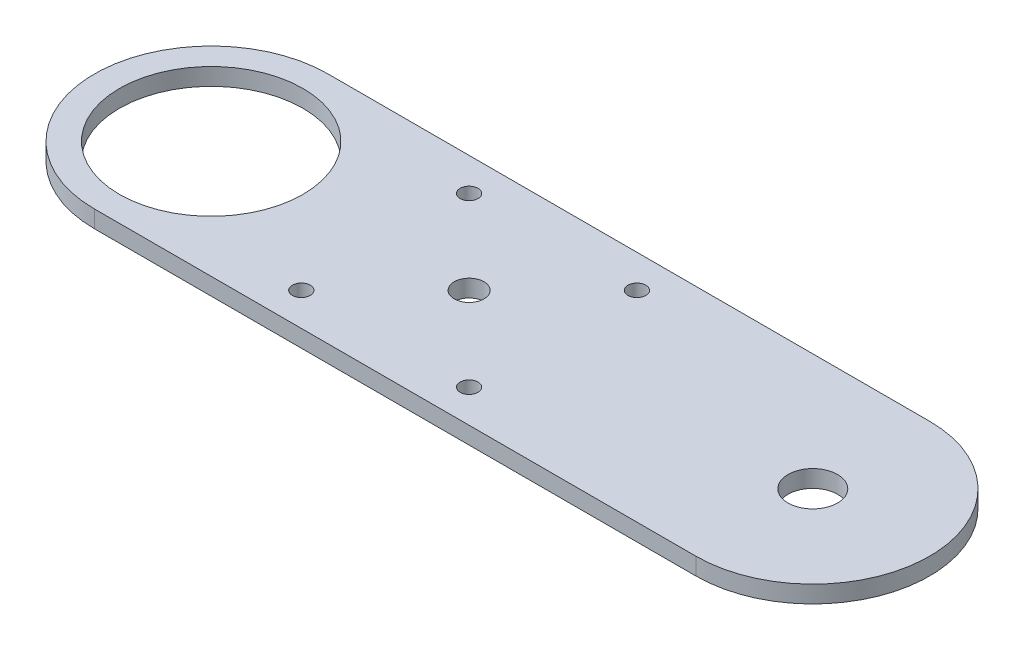
SolidWorks part; units mm, degrees
ref_plane "Front Plane" through (0, 0, 0) normal (0, 0, 1) x (1, 0, 0)
ref_plane "Top Plane" through (0, 0, 0) normal (0, 1, 0) x (1, 0, 0)
ref_plane "Right Plane" through (0, 0, 0) normal (1, 0, 0) x (0, 0, -1)
sketch "Sketch1" plane through (0, 0, 0) normal (0, 1, 0) x (1, 0, 0)
  line L0 (0, 0) -> (111.1504, 0) construction
  line L1 (0, 21.59) -> (111.1504, 21.59)
  line L2 (0, -21.59) -> (111.1504, -21.59)
  line L3 (55.5752, 21.59) -> (55.5752, -21.59) construction
  line L4 (0, 0) -> (111.1504, 0) construction
  line L5 (32.1504, -15.5) -> (63.1504, -15.5) construction
  line L6 (32.1504, -15.5) -> (32.1504, 15.5) construction
  line L7 (32.1504, 15.5) -> (63.1504, 15.5) construction
  line L8 (63.1504, -15.5) -> (63.1504, 15.5) construction
  line L9 (32.1504, -15.5) -> (63.1504, 15.5) construction
  line L10 (32.1504, 15.5) -> (63.1504, -15.5) construction
  line L11 (32.1504, 0) -> (63.1504, 0) construction
  line L12 (47.6504, -15.5) -> (47.6504, 15.5) construction
  arc A0 (0, 21.59) -> (0, -21.59) centre (0, 0) ccw
  arc A1 (111.1504, -21.59) -> (111.1504, 21.59) centre (111.1504, 0) ccw
  circle A2 centre (0, 0) radius 16.9545
  circle A3 centre (111.1504, 0) radius 4.572
  circle A4 centre (47.6504, 0) radius 2.75
  circle A5 centre (32.1504, -15.5) radius 1.651
  circle A6 centre (32.1504, 15.5) radius 1.651
  circle A7 centre (63.1504, 15.5) radius 1.651
  circle A8 centre (63.1504, -15.5) radius 1.651
  point P3 (55.5752, 0)
  dimension "D2" = 21.59
  dimension "D3" = 33.909
  dimension "D4" = 9.144
  dimension "D5" = 5.5
  dimension "D7" = 3.302
  dimension "D10" = 3.302
  dimension "D1" = 111.1504
  dimension "D6" = 63.5
  dimension "D8" = 31
  dimension "D9" = 31
extrude "Boss-Extrude1" add sketch "Sketch1" along normal blind 3.175
